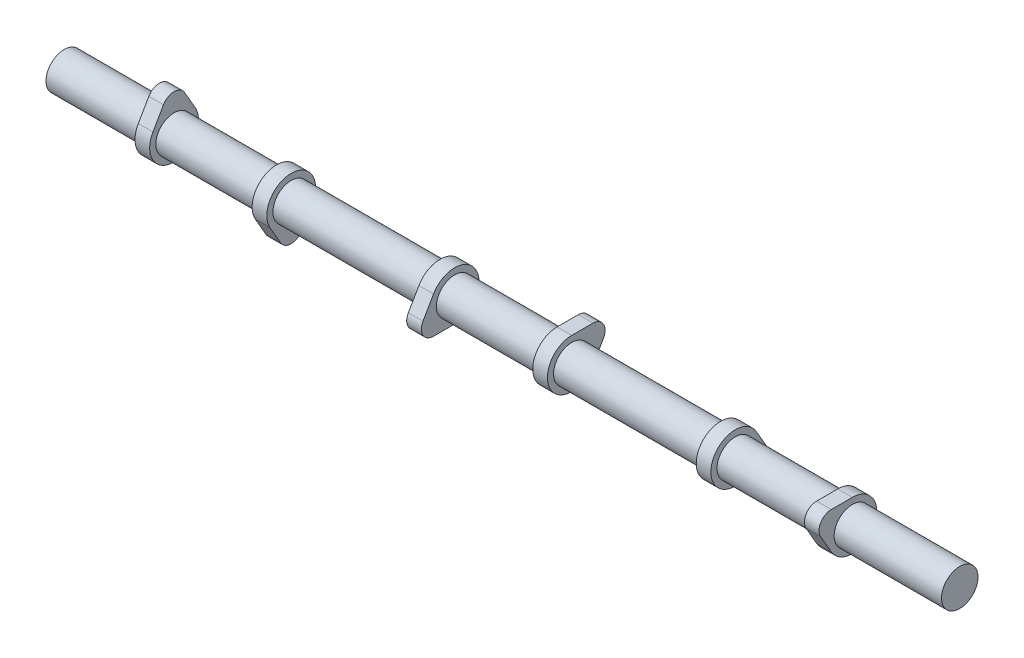
SolidWorks part; units mm, degrees
ref_plane "Front Plane" through (0, 0, 0) normal (0, 0, 1) x (1, 0, 0)
ref_plane "Top Plane" through (0, 0, 0) normal (0, 1, 0) x (1, 0, 0)
ref_plane "Right Plane" through (0, 0, 0) normal (1, 0, 0) x (0, 0, -1)
sketch "Sketch1" plane through (0, 0, 0) normal (1, 0, 0) x (0, 0, -1)
  line L0 (-10.9985, 6.35) -> (-5.4993, 15.875)
  line L1 (5.4993, 15.875) -> (10.9985, 6.35)
  arc A0 (-10.9985, 6.35) -> (10.9985, 6.35) centre (0, 0) ccw
  arc A1 (5.4993, 15.875) -> (-5.4993, 15.875) centre (0, 12.7) ccw
  dimension "D1" = 25.4
  dimension "D3" = 12.7
  dimension "D2" = 12.7
extrude "Boss-Extrude1" add sketch "Sketch1" along normal mid plane 7.62
ref_axis "Axis1" through (427.4504, 0, 0) along (-1, 0, 0)
move or copy body "Body-Move/Copy1" bodies to move or copy 101 copy yes number of copies 1 translate (60.96, 0, 0)
move or copy body "Body-Move/Copy2" bodies to move or copy 102 copy no rotation origin (0, 0, 0) rotation axis (1, 0, 0) rotation angle 180
sketch "Sketch2" plane through (0, 0, 0) normal (1, 0, 0) x (0, 0, -1)
  circle A0 centre (0, 0) radius 9.5
  dimension "D1" = 19
extrude "Boss-Extrude3" add sketch "Sketch2" along normal blind 146.05 from offset 25.4 offset against normal yes
pattern_linear "LPattern1" count 3 spacing 146.05 along (1, 0, 0) of bodies 105
move or copy body "Body-Move/Copy3" bodies to move or copy 106 copy no rotation origin (0, 0, 0) rotation axis (1, 0, 0) rotation angle 120
move or copy body "Body-Move/Copy4" bodies to move or copy 107 copy no rotation origin (0, 0, 0) rotation axis (-1, 0, 0) rotation angle 120
sketch "Sketch3" plane through (-25.4, 0, 0) normal (-1, 0, 0) x (0, 0, 1)
  circle A1 centre (0, 0) radius 9.5
  circle A2 centre (0, 0) radius 9.5
  dimension "D1" = 0
extrude "Boss-Extrude4" add sketch "Sketch3" along normal blind 27.94 contours A2
combine bodies "Combine1" operation type add bodies to combine 108 110 109
